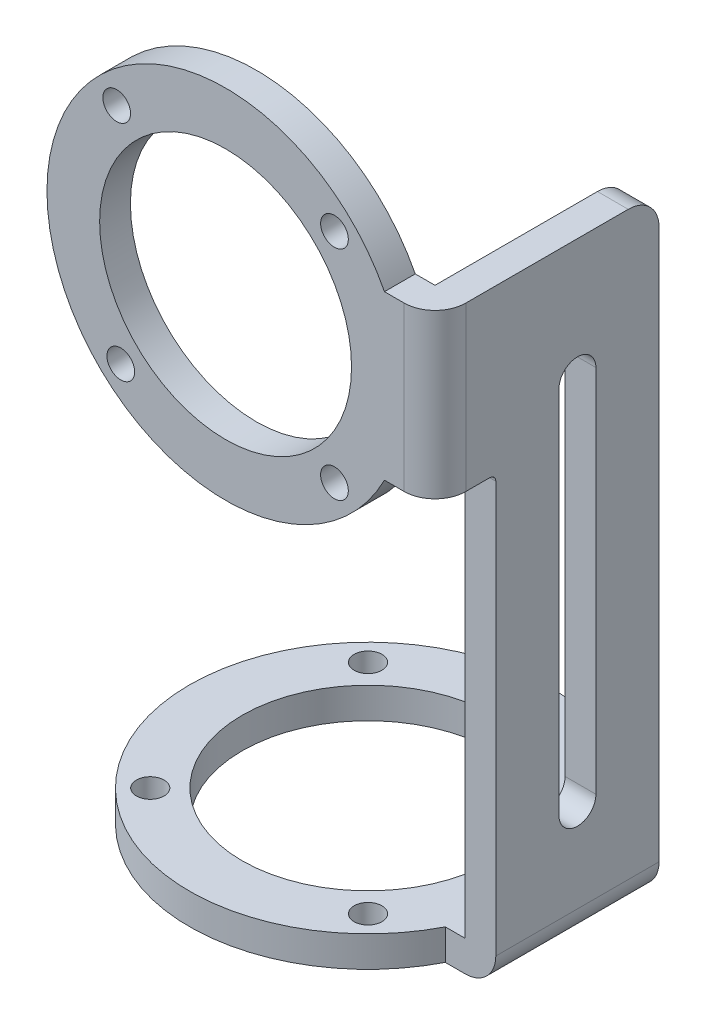
SolidWorks part; units mm, degrees
material "Wrought Stainless Steel"
ref_plane "Front Plane" through (0, 0, 0) normal (0, 0, 1) x (1, 0, 0)
ref_plane "Top Plane" through (0, 0, 0) normal (0, 1, 0) x (1, 0, 0)
ref_plane "Right Plane" through (0, 0, 0) normal (1, 0, 0) x (0, 0, -1)
sketch "Sketch1" plane through (0, 0, 0) normal (0, 0, 1) x (1, 0, 0)
  line L0 (29, 28.1725) -> (29, -28.1725) construction
  line L1 (0, 13.25) -> (29, 13.25)
  line L2 (0, -13.25) -> (29, -13.25)
  circle A0 centre (0, 0) radius 29
  circle A1 centre (0, 0) radius 20.45
  circle A2 centre (0, 0) radius 13.25
  point P8 (29, 0)
  point P11 (0, 13.25)
  point P14 (0, -13.25)
extrude "Boss-Extrude2" add sketch "Sketch1" along normal blind 5 contours A1 L1 A0 L2 | A1 L2 A0 L1 | L0 L1 A0 | L0 A0 L2 region at (28.0487, 9.9752, 0) region at (23.3721, 0, 0) region at (28.0487, -9.9752, 0) region at (20.6865, 14.0479, 0)
sketch "Sketch2" plane through (29, 0, 0) normal (1, 0, 0) x (0, 0, -1)
  line L0 (0, 13.25) -> (26.375, 13.25)
  line L1 (0, -13.25) -> (31.375, -13.25)
  line L3 (0, 13.25) -> (0, -13.25)
  line L4 (0, -13.25) -> (0, -81)
  line L6 (0, -81) -> (31.375, -81)
  line L7 (31.375, 8.25) -> (31.375, -81)
  arc A1 (26.375, 13.25) -> (31.375, 8.25) centre (26.375, 8.25) cw
  dimension "D1" = 5
extrude "Boss-Extrude3" add sketch "Sketch2" along normal blind 5 separate body contours L4 L6 L7 A1 L0 L3
sketch "Sketch14" plane through (0, -81, 0) normal (0, -1, 0) x (1, 0, 0)
  line L3 (29, 13.2074) -> (29, -49.4574) construction
  line L4 (0, -4.875) -> (29, -4.875)
  line L5 (0, -31.375) -> (29, -31.375)
  circle A3 centre (0, -18.125) radius 29
  circle A4 centre (0, -18.125) radius 20.45
  circle A5 centre (0, -18.125) radius 13.25
  point P16 (29, -18.125)
  line M7 (29, 0) -> (29, -31.375)
extrude "Boss-Extrude6" add sketch "Sketch14" along normal blind 5 separate body contours A4 L5 A3 L4 | A4 L4 A3 L5 | A3 L4 M7 | A3 L5 M7 region at (-21.2479, -81, -18.125) region at (23.3721, -81, -18.125) region at (28.0487, -81, -8.1498) region at (28.0487, -81, -28.1002)
sketch "Sketch17" plane through (34, 0, 0) normal (1, 0, 0) x (0, 0, -1)
  line L0 (0, -13.25) -> (3.875, -13.25)
  line L1 (4.875, -81) -> (4.875, -14.25)
  line L2 (0, -13.25) -> (0, -81)
  line L3 (4.875, -81) -> (0, -81)
  arc A0 (4.875, -14.25) -> (3.875, -13.25) centre (3.875, -14.25) ccw
  dimension "D1" = 1
extrude "Cut-Extrude2" cut sketch "Sketch17" against normal blind 5 contours L1 A0 L0 L2 L3
sketch "Sketch21" plane through (0, 13.25, 0) normal (0, 1, 0) x (1, 0, 0)
  line L0 (29, 0) -> (34, 0)
  line L1 (34, 0) -> (29, 0) construction
  line L2 (34, 0) -> (34, 26.375) construction
  line L3 (29, 0) -> (29, -5)
  arc A0 (29, -5) -> (34, 0) centre (29, 0) ccw
  line M2 (29, 0) -> (34, 0)
extrude "Boss-Extrude7" add sketch "Sketch21" against normal blind 26.5 contours L3 A0 M2 region at (31.1221, 13.25, 2.1221)
sketch "Sketch22" plane through (0, 0, -4.875) normal (0, 0, 1) x (1, 0, 0)
  line L0 (29, -81) -> (29, -86)
  line L1 (29, -86) -> (29, -81) construction
  line L2 (29, -81) -> (34, -81)
  arc A0 (29, -86) -> (34, -81) centre (29, -81) ccw
  line M4 (29, -86) -> (29, -81)
extrude "Boss-Extrude8" add sketch "Sketch22" against normal blind 26.5 contours A0 L2 M4 region at (31.1221, -83.1221, -4.875)
sketch "Sketch23" plane through (34, 0, 0) normal (1, 0, 0) x (0, 0, -1)
  line L0 (15.125, -36.375) -> (21.125, -36.375)
  line L2 (18.125, -81) -> (18.125, -36.375) construction
  line L3 (31.375, -81) -> (4.875, -81) construction
  line L4 (21.125, -6.375) -> (21.125, -66.375)
  line L5 (15.125, -6.375) -> (15.125, -66.375)
  arc A0 (21.125, -66.375) -> (15.125, -66.375) centre (18.125, -66.375) cw
  arc A1 (21.125, -6.375) -> (15.125, -6.375) centre (18.125, -6.375) ccw
  point P3 (18.125, -36.375)
  point P10 (21.125, -36.375)
  point P13 (15.125, -36.375)
extrude "Cut-Extrude3" cut sketch "Sketch23" against normal blind 26.5 contours L4 A1 L5 L0 | L2 A0 L4 L0 | A0 L2 L0 L5 region at (34, -20.19, -18.125) region at (34, -52.56, -16.6415) region at (34, -52.56, -19.6085)
sketch "Sketch24" plane through (0, 0, 5) normal (0, 0, 1) x (1, 0, 0)
  line L0 (0, 0) -> (17.6777, 17.6777)
  line L1 (0, 0) -> (17.6777, -17.6777)
  line L2 (0, 0) -> (-17.6777, 17.6777)
  line L3 (0, 0) -> (-17.6777, -17.6777)
  circle A0 centre (0, 0) radius 25
  circle A1 centre (17.6777, 17.6777) radius 2.25
  circle A2 centre (17.6777, -17.6777) radius 2.25
  circle A3 centre (-17.6777, 17.6777) radius 2.25
  circle A4 centre (-17.0153, -18.3161) radius 2.25
extrude "Cut-Extrude5" cut sketch "Sketch24" against normal blind 10 contours A4 | A3 | A1 | A2
sketch "Sketch25" plane through (0, -86, 0) normal (0, -1, 0) x (1, 0, 0)
  line L0 (0, -18.125) -> (17.6777, -0.4473)
  line L1 (0, -18.125) -> (17.6777, -35.8027)
  line L2 (0, -18.125) -> (-17.6777, -35.8027)
  line L3 (0, -18.125) -> (-17.6777, -0.4473)
  circle A0 centre (0, -18.125) radius 25
  circle A1 centre (-17.6777, -0.4473) radius 2.25
  circle A2 centre (17.6777, -0.4473) radius 2.25
  circle A3 centre (17.6777, -35.8027) radius 2.25
  circle A4 centre (-17.6777, -35.8027) radius 2.25
extrude "Cut-Extrude6" cut sketch "Sketch25" against normal blind 10 contours A1 | A2 | A3 | A4
